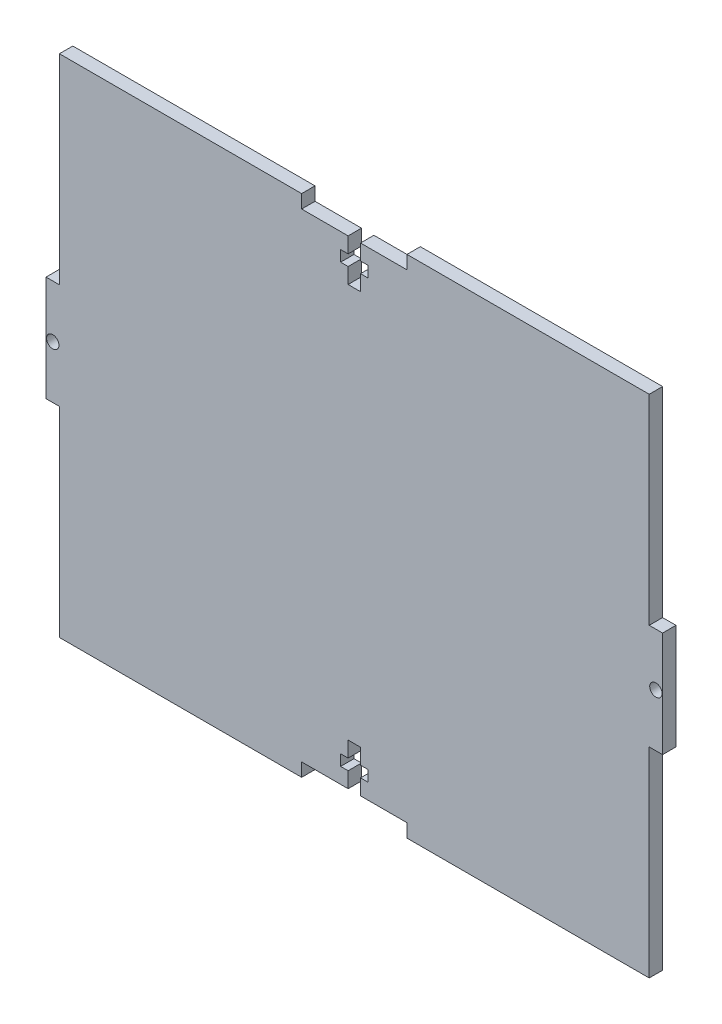
SolidWorks part; units mm, degrees
ref_plane "Front Plane" through (0, 0, 0) normal (0, 0, 1) x (1, 0, 0)
ref_plane "Top Plane" through (0, 0, 0) normal (0, 1, 0) x (1, 0, 0)
ref_plane "Right Plane" through (0, 0, 0) normal (1, 0, 0) x (0, 0, -1)
sketch "Sketch1" plane through (0, 0, 0) normal (0, 0, 1) x (1, 0, 0)
  line L0 (0, 60) -> (0, -60) construction
  line L1 (-70, 60) -> (70, 60)
  line L2 (-70, 60) -> (-70, -60)
  line L3 (-70, -60) -> (70, -60)
  line L4 (70, 60) -> (70, -60)
  line L5 (-70, 60) -> (70, -60) construction
  line L6 (-70, -60) -> (70, 60) construction
  line L7 (-70, 0) -> (70, 0) construction
  line L8 (-3.25, -50.525) -> (3.25, -50.525)
  line L9 (12.5, 60) -> (-12.5, 60)
  line L10 (12.5, 60) -> (12.5, 56.825)
  line L11 (12.5, 56.825) -> (-12.5, 56.825)
  line L12 (-12.5, 60) -> (-12.5, 56.825)
  line L13 (12.5, 60) -> (-12.5, 56.825) construction
  line L14 (12.5, 56.825) -> (-12.5, 60) construction
  line L15 (-1.47, 56.825) -> (1.47, 56.825)
  line L16 (-1.47, 56.825) -> (-1.47, 46.825)
  line L17 (-1.47, 46.825) -> (1.47, 46.825)
  line L18 (1.47, 56.825) -> (1.47, 46.825)
  line L19 (-1.47, 56.825) -> (1.47, 46.825) construction
  line L20 (-1.47, 46.825) -> (1.47, 56.825) construction
  line L21 (-3.25, 53.125) -> (3.25, 53.125)
  line L22 (-3.25, 53.125) -> (-3.25, 50.525)
  line L23 (-3.25, 50.525) -> (3.25, 50.525)
  line L24 (3.25, 53.125) -> (3.25, 50.525)
  line L25 (-3.25, 53.125) -> (3.25, 50.525) construction
  line L26 (-3.25, 50.525) -> (3.25, 53.125) construction
  line L27 (3.25, -53.125) -> (3.25, -50.525)
  line L28 (-3.25, -53.125) -> (3.25, -53.125)
  line L29 (-3.25, -53.125) -> (-3.25, -50.525)
  line L30 (-1.47, -46.825) -> (1.47, -46.825)
  line L31 (1.47, -56.825) -> (1.47, -46.825)
  line L32 (-1.47, -56.825) -> (1.47, -56.825)
  line L33 (-1.47, -56.825) -> (-1.47, -46.825)
  line L34 (12.5, -56.825) -> (-12.5, -56.825)
  line L35 (-12.5, -60) -> (-12.5, -56.825)
  line L36 (12.5, -60) -> (-12.5, -60)
  line L37 (12.5, -60) -> (12.5, -56.825)
  line L38 (73.175, -12.5) -> (70, -12.5)
  line L39 (-73.175, 12.5) -> (-70, 12.5)
  line L40 (-73.175, 12.5) -> (-73.175, -12.5)
  line L41 (-73.175, -12.5) -> (-70, -12.5)
  line L42 (-70, 12.5) -> (-70, -12.5)
  line L43 (-73.175, 12.5) -> (-70, -12.5) construction
  line L44 (-73.175, -12.5) -> (-70, 12.5) construction
  line L45 (70, 12.5) -> (70, -12.5)
  line L46 (73.175, 12.5) -> (70, 12.5)
  line L47 (73.175, 12.5) -> (73.175, -12.5)
  circle A0 centre (-71.5875, 0) radius 1.47
  circle A1 centre (71.5875, 0) radius 1.47
  point P0 (0, 0)
  point P10 (0, 58.4125)
  point P15 (0, 51.825)
  point P20 (0, 51.825)
  point P37 (-71.5875, 0)
  dimension "D11" = 2.94
  dimension "D1" = 120
  dimension "D2" = 140
  dimension "D3" = 3.175
  dimension "D4" = 10
  dimension "D5" = 2.94
  dimension "D6" = 25
  dimension "D7" = 6.5
  dimension "D8" = 2.6
  dimension "D9" = 6.3
  dimension "D10" = 3.175
extrude "Boss-Extrude1" add sketch "Sketch1" along normal mid plane 3.175 contours L21 L24 L23 L18 L17 L16 L22 L11 L12 L1 L2 L3 L4 L10 | L40 L39 L42 L41 | A0 | L38 L45 L46 L47 | A1 region at (0, 0, 0)
